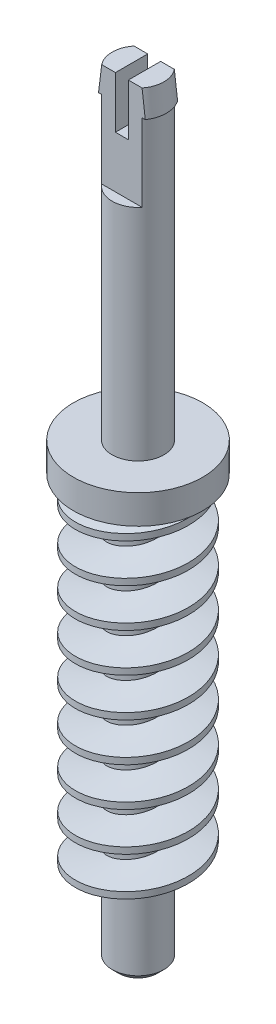
SolidWorks part; units mm, degrees
ref_plane "前视基准面" through (0, 0, 0) normal (0, 0, 1) x (1, 0, 0)
ref_plane "上视基准面" through (0, 0, 0) normal (0, 1, 0) x (1, 0, 0)
ref_plane "右视基准面" through (0, 0, 0) normal (1, 0, 0) x (0, 0, -1)
sketch "草图1" plane through (0, 0, 0) normal (0, 1, 0) x (1, 0, 0)
  circle A0 centre (0, 0) radius 2
  dimension "D1" = 4
extrude "凸台-拉伸1" add sketch "草图1" along normal blind 60
sketch "草图2" plane through (0, 0, 0) normal (0, 0, 1) x (1, 0, 0)
  line L0 (0, 60) -> (0, 58)
  line L1 (2, 60) -> (-2, 60) construction
  line L2 (0, 58) -> (-2.2, 58)
  line L3 (0, 60) -> (-2, 60)
  line L4 (-2, 60) -> (-2, 0) construction
  line L5 (-2, 60) -> (-2.2, 58)
  dimension "D1" = 2
  dimension "D2" = 2.2
revolve "旋转1" add sketch "草图2" angle 360 about L0
sketch "草图3" plane through (0, 60, 0) normal (0, 1, 0) x (1, 0, 0)
  line L0 (0, 0) -> (0, -1.25) construction
  line L1 (0, -1.25) -> (0, -2.25) construction
  line L2 (0, 0) -> (1.1424, 0) construction
  line L3 (-3, -1.25) -> (3, -1.25)
  line L4 (-3, -2.25) -> (3, -2.25)
  line L5 (3, -1.25) -> (3, -2.25)
  line L6 (-3, -1.25) -> (-3, -2.25)
  line L7 (3, 1.25) -> (3, 2.25)
  line L8 (-3, 2.25) -> (3, 2.25)
  line L9 (-3, 1.25) -> (-3, 2.25)
  line L10 (-3, 1.25) -> (3, 1.25)
  dimension "D1" = 1.25
  dimension "D2" = 1
  dimension "D3" = 3
extrude "切除-拉伸1" cut sketch "草图3" against normal blind 8
sketch "草图4" plane through (0, 60, 0) normal (0, 1, 0) x (1, 0, 0)
  line L0 (-0.5, 1.25) -> (-0.5, -1.25)
  line L1 (-0.5, 1.25) -> (0.5, 1.25)
  line L2 (-0.5, -1.25) -> (0.5, -1.25)
  line L3 (0.5, 1.25) -> (0.5, -1.25)
  line L4 (-0.5, 1.25) -> (0.5, -1.25) construction
  line L5 (-0.5, -1.25) -> (0.5, 1.25) construction
  point P2 (0, 0)
  dimension "D1" = 1
extrude "切除-拉伸2" cut sketch "草图4" against normal blind 4
ref_plane "基准面2" through (0, 5.75, 0) normal (0, -1, 0) x (-1, 0, 0)
sketch "草图5" plane through (0, 5.75, 0) normal (0, -1, 0) x (-1, 0, 0)
  circle A0 centre (0, 0) radius 4.4
  dimension "D1" = 8.8
curve "螺旋线/涡状线1" pitch 3 height 27 radius 4.4 centre (0, 5.75, 0) axis (0, 1, 0) start towards (0, 0, -1)
ref_plane "基准面3" through (0, 35, 0) normal (0, -1, 0) x (-1, 0, 0)
sketch "草图6" plane through (0, 0, 0) normal (1, 0, 0) x (0, 0, -1)
  line L0 (2, 0) -> (2, 5.75)
  line L1 (-2.2, 5.75) -> (2.2, 5.75) construction
  line L2 (2, 0) -> (2, 52) construction
  line L3 (2, 5.75) -> (4.4, 5.75) construction
  line L4 (4.4, 5.5) -> (4.4, 6)
  line L5 (4.4, 6) -> (2, 6.5)
  line L6 (2, 6.5) -> (2, 5)
  line L7 (4.4, 5.5) -> (2, 5)
  spline S0 degree 3 poles (4.4, 5.75) (4.4, 5.8121) (4.1709, 5.9377) (3.1923, 6.125) (1.7276, 6.3125) (0, 6.5) (-1.7276, 6.6875) (-3.1923, 6.875) (-4.1709, 7.0625) (-4.5145, 7.25) (-4.1709, 7.4375) (-3.1923, 7.625) (-1.7276, 7.8125) (0, 8) (1.7276, 8.1875) (3.1923, 8.375) (4.1709, 8.5625) (4.5145, 8.75) (4.1709, 8.9375) (3.1923, 9.125) (1.7276, 9.3125) (0, 9.5) (-1.7276, 9.6875) (-3.1923, 9.875) (-4.1709, 10.0625) (-4.5145, 10.25) (-4.1709, 10.4375) (-3.1923, 10.625) (-1.7276, 10.8125) (0, 11) (1.7276, 11.1875) (3.1923, 11.375) (4.1709, 11.5625) (4.5145, 11.75) (4.1709, 11.9375) (3.1923, 12.125) (1.7276, 12.3125) (0, 12.5) (-1.7276, 12.6875) (-3.1923, 12.875) (-4.1709, 13.0625) (-4.5145, 13.25) (-4.1709, 13.4375) (-3.1923, 13.625) (-1.7276, 13.8125) (0, 14) (1.7276, 14.1875) (3.1923, 14.375) (4.1709, 14.5625) (4.5145, 14.75) (4.1709, 14.9375) (3.1923, 15.125) (1.7276, 15.3125) (0, 15.5) (-1.7276, 15.6875) (-3.1923, 15.875) (-4.1709, 16.0625) (-4.5145, 16.25) (-4.1709, 16.4375) (-3.1923, 16.625) (-1.7276, 16.8125) (0, 17) (1.7276, 17.1875) (3.1923, 17.375) (4.1709, 17.5625) (4.5145, 17.75) (4.1709, 17.9375) (3.1923, 18.125) (1.7276, 18.3125) (0, 18.5) (-1.7276, 18.6875) (-3.1923, 18.875) (-4.1709, 19.0625) (-4.5145, 19.25) (-4.1709, 19.4375) (-3.1923, 19.625) (-1.7276, 19.8125) (0, 20) (1.7276, 20.1875) (3.1923, 20.375) (4.1709, 20.5625) (4.5145, 20.75) (4.1709, 20.9375) (3.1923, 21.125) (1.7276, 21.3125) (0, 21.5) (-1.7276, 21.6875) (-3.1923, 21.875) (-4.1709, 22.0625) (-4.5145, 22.25) (-4.1709, 22.4375) (-3.1923, 22.625) (-1.7276, 22.8125) (0, 23) (1.7276, 23.1875) (3.1923, 23.375) (4.1709, 23.5625) (4.5145, 23.75) (4.1709, 23.9375) (3.1923, 24.125) (1.7276, 24.3125) (0, 24.5) (-1.7276, 24.6875) (-3.1923, 24.875) (-4.1709, 25.0625) (-4.5145, 25.25) (-4.1709, 25.4375) (-3.1923, 25.625) (-1.7276, 25.8125) (0, 26) (1.7276, 26.1875) (3.1923, 26.375) (4.1709, 26.5625) (4.5145, 26.75) (4.1709, 26.9375) (3.1923, 27.125) (1.7276, 27.3125) (0, 27.5) (-1.7276, 27.6875) (-3.1923, 27.875) (-4.1709, 28.0625) (-4.5145, 28.25) (-4.1709, 28.4375) (-3.1923, 28.625) (-1.7276, 28.8125) (0, 29) (1.7276, 29.1875) (3.1923, 29.375) (4.1709, 29.5625) (4.5145, 29.75) (4.1709, 29.9375) (3.1923, 30.125) (1.7276, 30.3125) (0, 30.5) (-1.7276, 30.6875) (-3.1923, 30.875) (-4.1709, 31.0625) (-4.5145, 31.25) (-4.1709, 31.4375) (-3.1923, 31.625) (-1.7276, 31.8125) (0, 32) (1.7276, 32.1875) (3.1923, 32.375) (4.1709, 32.5623) (4.4, 32.6879) (4.4, 32.75) knots 0 0 0 0 0.006944 0.013889 0.020833 0.027778 0.034722 0.041667 0.048611 0.055556 0.0625 0.069444 0.076389 0.083333 0.090278 0.097222 0.104167 0.111111 0.118056 0.125 0.131944 0.138889 0.145833 0.152778 0.159722 0.166667 0.173611 0.180556 0.1875 0.194444 0.201389 0.208333 0.215278 0.222222 0.229167 0.236111 0.243056 0.25 0.256944 0.263889 0.270833 0.277778 0.284722 0.291667 0.298611 0.305556 0.3125 0.319444 0.326389 0.333333 0.340278 0.347222 0.354167 0.361111 0.368056 0.375 0.381944 0.388889 0.395833 0.402778 0.409722 0.416667 0.423611 0.430556 0.4375 0.444444 0.451389 0.458333 0.465278 0.472222 0.479167 0.486111 0.493056 0.5 0.506944 0.513889 0.520833 0.527778 0.534722 0.541667 0.548611 0.555556 0.5625 0.569444 0.576389 0.583333 0.590278 0.597222 0.604167 0.611111 0.618056 0.625 0.631944 0.638889 0.645833 0.652778 0.659722 0.666667 0.673611 0.680556 0.6875 0.694444 0.701389 0.708333 0.715278 0.722222 0.729167 0.736111 0.743056 0.75 0.756944 0.763889 0.770833 0.777778 0.784722 0.791667 0.798611 0.805556 0.8125 0.819444 0.826389 0.833333 0.840278 0.847222 0.854167 0.861111 0.868056 0.875 0.881944 0.888889 0.895833 0.902778 0.909722 0.916667 0.923611 0.930556 0.9375 0.944444 0.951389 0.958333 0.965278 0.972222 0.979167 0.986111 0.993056 1 1 1 1 construction
  dimension "D1" = 0.25
  dimension "D2" = 0.75
sweep "扫描1" add profiles "草图6" path "螺旋线/涡状线1"
sketch "草图7" plane through (0, 35, 0) normal (0, -1, 0) x (-1, 0, 0)
  circle A0 centre (0, 0) radius 5
  dimension "D1" = 10
extrude "凸台-拉伸2" add sketch "草图7" along normal blind 2.25
chamfer "倒角1" distance 0.5 angle 45 1 edges at (0, 0, 2)
